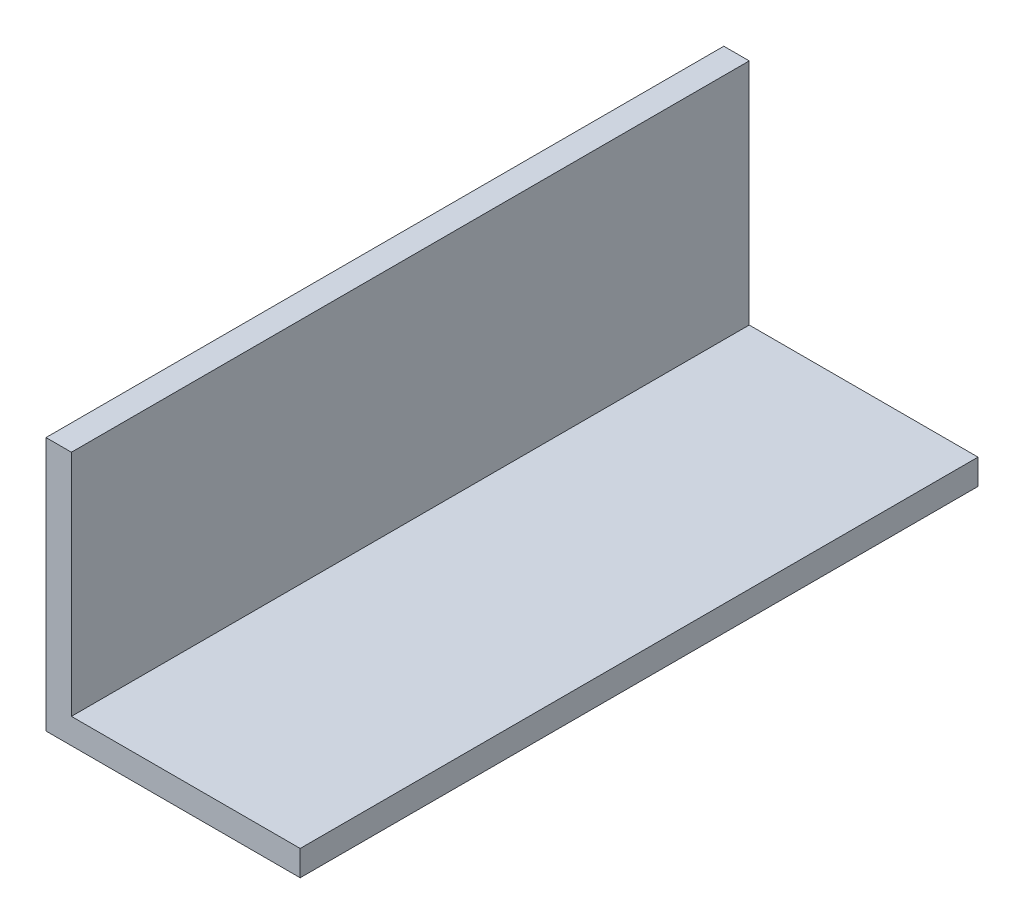
SolidWorks part; units mm, degrees
ref_plane "Спереди" through (0, 0, 0) normal (0, 0, 1) x (1, 0, 0)
ref_plane "Сверху" through (0, 0, 0) normal (0, 1, 0) x (1, 0, 0)
ref_plane "Справа" through (0, 0, 0) normal (1, 0, 0) x (0, 0, -1)
sketch "Эскиз1" plane through (0, 0, 0) normal (0, 0, 1) x (1, 0, 0)
  line L0 (0, 30) -> (0, 0)
  line L1 (0, 0) -> (30, 0)
  line L2 (0, 30) -> (3, 30)
  line L3 (3, 30) -> (3, 3)
  line L4 (3, 3) -> (30, 3)
  line L5 (30, 3) -> (30, 0)
extrude "Бобышка-Вытянуть1" add sketch "Эскиз1" along normal blind 80
